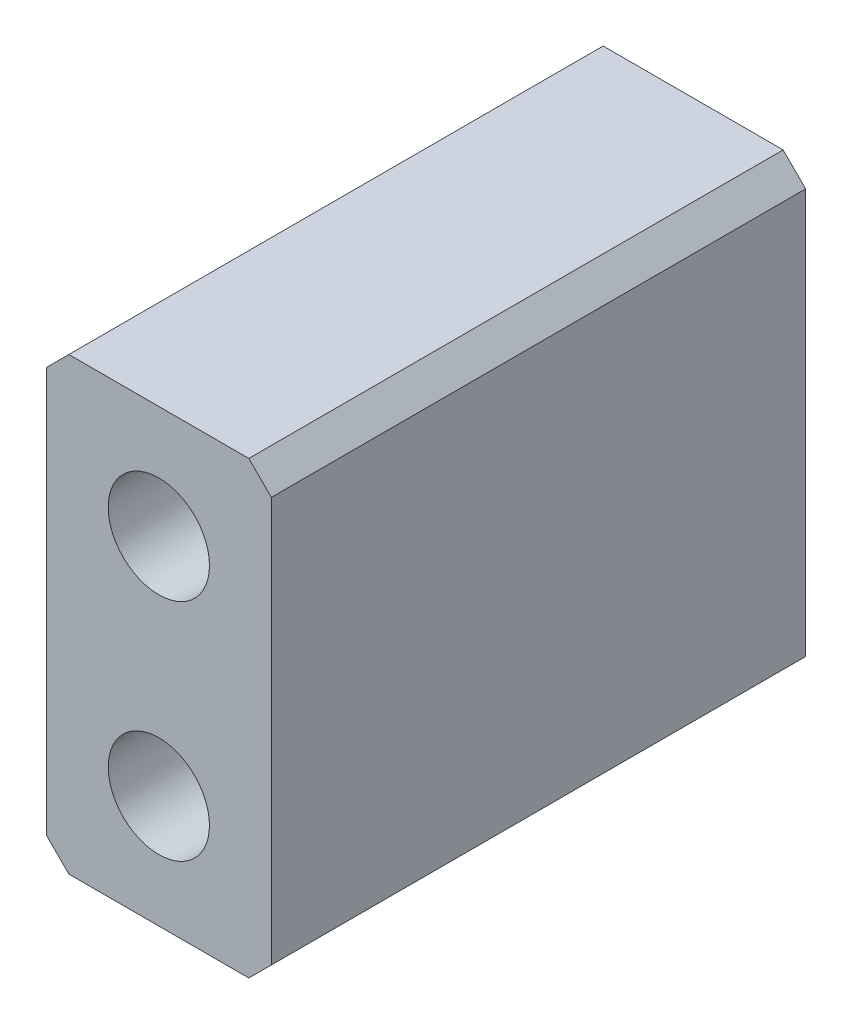
SolidWorks part; units mm, degrees
ref_plane "前视基准面" through (0, 0, 0) normal (0, 0, 1) x (1, 0, 0)
ref_plane "上视基准面" through (0, 0, 0) normal (0, 1, 0) x (1, 0, 0)
ref_plane "右视基准面" through (0, 0, 0) normal (1, 0, 0) x (0, 0, -1)
sketch "草图1" plane through (0, 0, 0) normal (0, 0, 1) x (1, 0, 0)
  line L0 (0, 0) -> (0, 10) construction
  line L1 (-10, 20) -> (10, 20)
  line L2 (-10, 20) -> (-10, -20)
  line L3 (-10, -20) -> (10, -20)
  line L4 (10, 20) -> (10, -20)
  line L5 (-10, 20) -> (10, -20) construction
  line L6 (-10, -20) -> (10, 20) construction
  line L7 (0, 0) -> (0, -10) construction
  circle A0 centre (0, 10) radius 4.5
  circle A1 centre (0, -10) radius 4.5
  point P0 (0, 0)
extrude "凸台-拉伸1" add sketch "草图1" along normal blind 47.5
chamfer "倒角1" distance 2 angle 45 1 edges at (-10, -20, 23.75)
chamfer "倒角2" distance 2 angle 45 3 edges at (10, -20, 23.75) (-10, 20, 23.75) (10, 20, 23.75)
